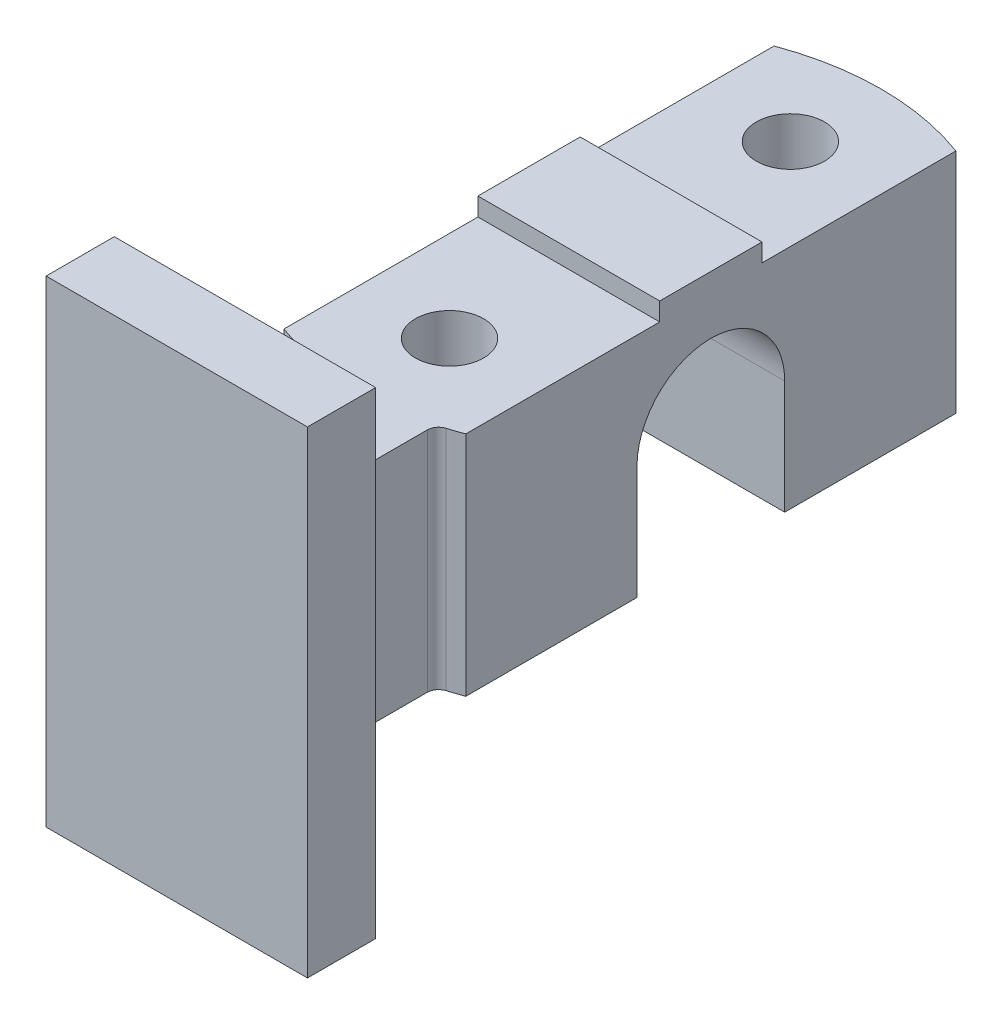
SolidWorks part; units mm, degrees
ref_plane "Front Plane" through (0, 0, 0) normal (0, 0, 1) x (1, 0, 0)
ref_plane "Top Plane" through (0, 0, 0) normal (0, 1, 0) x (1, 0, 0)
ref_plane "Right Plane" through (0, 0, 0) normal (1, 0, 0) x (0, 0, -1)
sketch "Sketch1" plane through (0, 0, 0) normal (0, 1, 0) x (1, 0, 0)
  line L0 (0, 226.9283) -> (0, -234.8875) construction
  line L1 (-367.6399, 0) -> (404.6759, 0) construction
  line L2 (-57.5, -165) -> (57.5, -165)
  line L3 (-40, 107.8193) -> (-40, -107.8193)
  line L4 (40, 107.8193) -> (40, -107.8193)
  line L5 (-30, -145) -> (-30, -114.7824)
  line L6 (30, -145) -> (30, -114.7824)
  line L7 (-57.5, -165) -> (-57.5, -195)
  line L8 (-57.5, -195) -> (57.5, -195)
  line L9 (57.5, -195) -> (57.5, -165)
  circle A0 centre (0, 75) radius 15
  circle A1 centre (0, -75) radius 15
  arc A2 (-40, -107.8193) -> (-33.5417, -109.9998) centre (0, 0) ccw
  arc A3 (40, 107.8193) -> (-40, 107.8193) centre (0, 0) ccw
  arc A4 (33.5417, -109.9998) -> (40, -107.8193) centre (0, 0) ccw
  arc A5 (30, -114.7824) -> (33.5417, -109.9998) centre (35, -114.7824) cw
  arc A6 (-30, -114.7824) -> (-33.5417, -109.9998) centre (-35, -114.7824) ccw
  arc A7 (-50, -165) -> (-30, -145) centre (-50, -145) ccw
  arc A8 (50, -165) -> (30, -145) centre (50, -145) cw
  point P7 (0, -165)
  point P23 (30, -111.018)
  point P26 (-30, -111.018)
  dimension "D2" = 30
  dimension "D6" = 230
  dimension "D10" = 5
  dimension "D11" = 20
  dimension "D1" = 115
  dimension "D3" = 150
  dimension "D4" = 75
  dimension "D5" = 90
  dimension "D7" = 80
  dimension "D8" = 40
  dimension "D9" = 30
  dimension "D12" = 30
extrude "Boss-Extrude1" add sketch "Sketch1" along normal mid plane 100 contours L2 A8 L6 A5 A4 L4 A3 L3 A2 A6 L5 A7 A0 A1 region at (0, 0, 23.0138)
extrude "Boss-Extrude2" add sketch "Sketch1<3>" along normal mid plane 210 contours L8 L9 L2 L7 region at (0, 0, 180)
sketch "Sketch1<3>" plane through (0, 0, 0) normal (0, 1, 0) x (1, 0, 0) same geometry as "Sketch1"
sketch "Sketch4" plane through (0, 50, 0) normal (0, 1, 0) x (1, 0, 0)
  line L0 (-40, 22.5) -> (40, 22.5)
  line L1 (-40, 107.8193) -> (-40, -107.8193) construction
  line L2 (40, 107.8193) -> (40, -107.8193) construction
  line L3 (-40, -22.5) -> (40, -22.5)
  line L4 (-40, 22.5) -> (-40, -22.5)
  line L5 (40, 22.5) -> (40, -22.5)
  dimension "D1" = 45
  dimension "D2" = 22.5
extrude "Boss-Extrude4" add sketch "Sketch4" along normal blind 8
sketch "Sketch5" plane through (0, -50, 0) normal (0, -1, 0) x (1, 0, 0)
  line L0 (-40, 22.5) -> (40, 22.5)
  line L1 (-40, -107.8193) -> (-40, 107.8193) construction
  line L2 (40, -107.8193) -> (40, 107.8193) construction
  line L3 (-40, -22.5) -> (40, -22.5)
  line L4 (-40, 22.5) -> (-40, -22.5)
  line L5 (40, 22.5) -> (40, -22.5)
  dimension "D1" = 45
extrude "Cut-Extrude1" cut sketch "Sketch5" against normal blind 8
sketch "Sketch6" plane through (-40, 0, 0) normal (-1, 0, 0) x (0, 0, 1)
  line L0 (-32.5, 0) -> (-32.5, -50)
  line L1 (-107.8193, -50) -> (-22.5, -50) construction
  line L2 (-32.5, -50) -> (32.5, -50)
  line L3 (22.5, -50) -> (107.8193, -50) construction
  line L4 (32.5, -50) -> (32.5, 0)
  arc A0 (32.5, 0) -> (-32.5, 0) centre (0, 0) ccw
  dimension "D1" = 65
extrude "Cut-Extrude2" cut sketch "Sketch6" against normal through all
fillet "Fillet1" radius 20 2 edges at (0, 50, 165) (0, -50, 165)
